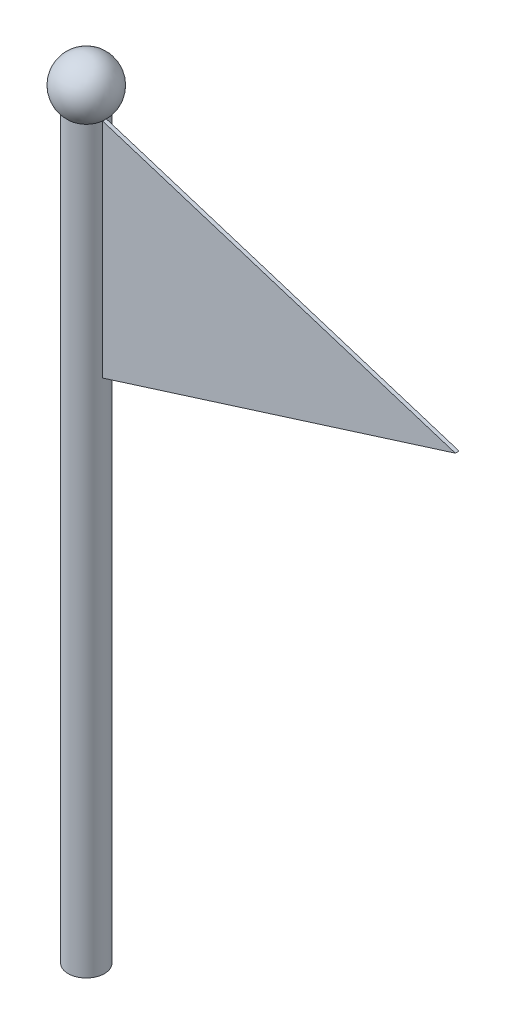
SolidWorks part; units mm, degrees
material "ABS PC"
ref_plane "Front Plane" through (0, 0, 0) normal (0, 0, 1) x (1, 0, 0)
ref_plane "Top Plane" through (0, 0, 0) normal (0, 1, 0) x (1, 0, 0)
ref_plane "Right Plane" through (0, 0, 0) normal (1, 0, 0) x (0, 0, -1)
ref_axis "X Axis" through (-88.99, 0, 0) along (1, 0, 0)
ref_axis "Y Axis" through (0, 55, 0) along (0, -1, 0)
ref_axis "Z Axis" through (0, 0, -88.99) along (0, 0, 1)
sketch "Sketch1" plane through (0, 0, 0) normal (0, 1, 0) x (1, 0, 0)
  circle A0 centre (0, 0) radius 24.5
  dimension "D1" = 49
extrude "Boss-Extrude1" add sketch "Sketch1" along normal blind 1000
sketch "Sketch2" plane through (0, 0, 0) normal (0, 0, 1) x (1, 0, 0)
  line L0 (24.5, 1000) -> (-24.5, 1000) construction
  line L1 (0, 1062.5) -> (0, 987.5)
  arc A0 (0, 987.5) -> (0, 1062.5) centre (0, 1025) ccw
  arc A1 (0, 1062.5) -> (0, 987.5) centre (0, 1025) ccw construction
  dimension "D1" = 25
  dimension "D2" = 75
revolve "Revolve5" add sketch "Sketch2" angle 360 about L1
sketch "Sketch3" plane through (0, 0, 0) normal (0, 0, 1) x (1, 0, 0)
  line L0 (24.5, 996.6099) -> (500, 846.6099)
  line L1 (500, 846.6099) -> (24.5, 696.6099)
  line L2 (24.5, 0) -> (24.5, 996.6099) construction
  line L3 (24.5, 696.6099) -> (0, 696.6099)
  line L4 (0, 696.6099) -> (0, 996.6099)
  line L5 (24.5, 996.6099) -> (-24.5, 996.6099) construction
  line L6 (0, 996.6099) -> (24.5, 996.6099)
  line L7 (500, 846.6099) -> (0, 846.6099) construction
  dimension "D1" = 300
  dimension "D2" = 500
extrude "Boss-Extrude2" add sketch "Sketch3" along normal mid plane 5
sketch "Sketch4" plane through (0, 0, 2.5) normal (0, 0, 1) x (1, 0, 0)
  line L0 (126.6481, 835.5127) -> (284.8702, 835.5127) construction
